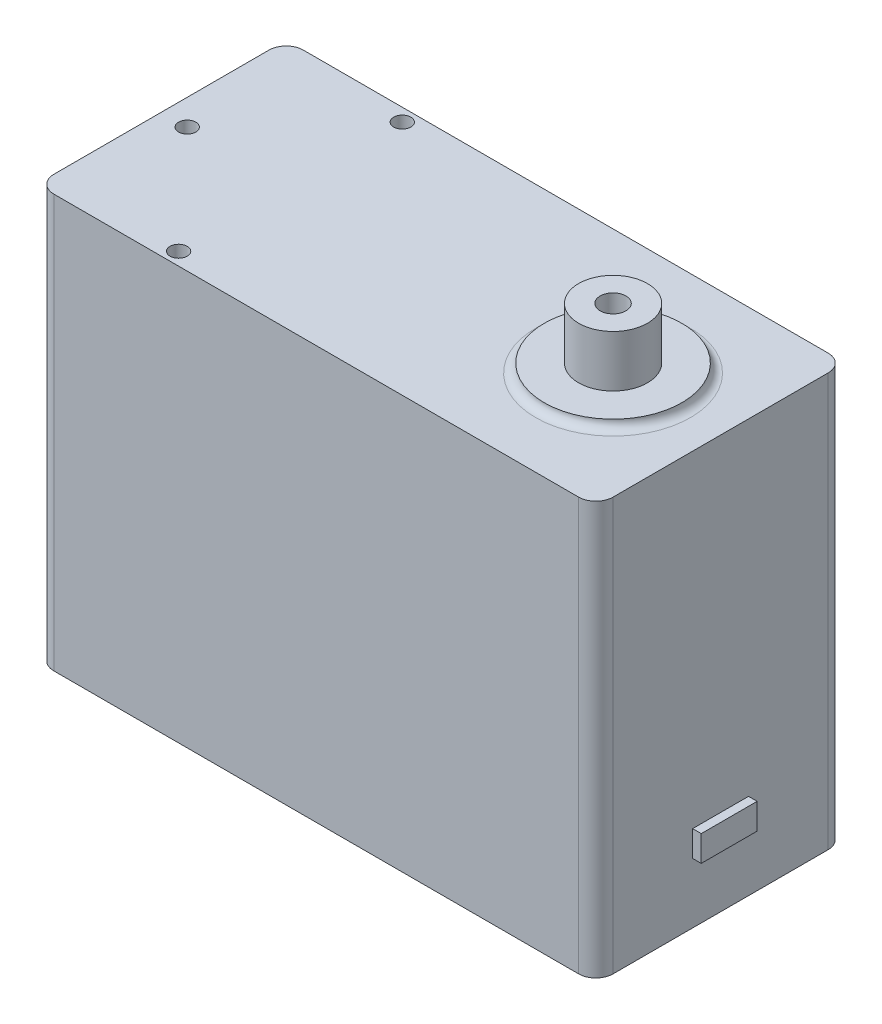
SolidWorks part; units mm, degrees
ref_plane "正面" through (0, 0, 0) normal (0, 0, 1) x (1, 0, 0)
ref_plane "平面" through (0, 0, 0) normal (0, 1, 0) x (1, 0, 0)
ref_plane "右側面" through (0, 0, 0) normal (1, 0, 0) x (0, 0, -1)
sketch "ｽｹｯﾁ2" plane through (0, 0, 0) normal (0, 1, 0) x (1, 0, 0)
  line L1 (-32.5, 14.5) -> (32.5, 14.5)
  line L2 (-32.5, 14.5) -> (-32.5, -14.5)
  line L3 (-32.5, -14.5) -> (32.5, -14.5)
  line L4 (32.5, 14.5) -> (32.5, -14.5)
  line L5 (-32.5, 14.5) -> (32.5, -14.5) construction
  line L6 (-32.5, -14.5) -> (32.5, 14.5) construction
  point P0 (0, 0)
  dimension "D1" = 65
  dimension "D2" = 29
extrude "ﾎﾞｽ - 押し出し1" add sketch "ｽｹｯﾁ2" along normal mid plane 48
fillet "ﾌｨﾚｯﾄ1" radius 2 4 edges at (32.5, 0, -14.5) (32.5, 0, 14.5) (-32.5, 0, 14.5) (-32.5, 0, -14.5)
sketch "ｽｹｯﾁ3" plane through (0, 24, 0) normal (0, 1, 0) x (1, 0, 0)
  line L0 (-32.5, 12.5) -> (-32.5, -12.5) construction
  line L1 (30.5, 14.5) -> (-30.5, 14.5) construction
  line L2 (-30.5, -14.5) -> (30.5, -14.5) construction
  line L3 (-26.4, 0) -> (26.4, 0) construction
  circle A0 centre (-29.5, 0) radius 1
  circle A1 centre (-17.5, -13) radius 1
  circle A2 centre (-17.5, 13) radius 1
  dimension "D1" = 2
  dimension "D4" = 2
  dimension "D2" = 3
  dimension "D3" = 14.5
  dimension "D5" = 15
  dimension "D6" = 1.5
extrude "ｶｯﾄ - 押し出し1" cut sketch "ｽｹｯﾁ3" against normal blind 6
sketch "ｽｹｯﾁ4" plane through (0, 24, 0) normal (0, 1, 0) x (1, 0, 0)
  line L0 (32.5, -12.5) -> (32.5, 12.5) construction
  line L1 (-30.5, -14.5) -> (30.5, -14.5) construction
  circle A0 centre (20, 0) radius 8
  dimension "D1" = 16
  dimension "D2" = 12.5
  dimension "D3" = 14.5
extrude "ﾎﾞｽ - 押し出し2" add sketch "ｽｹｯﾁ4" along normal blind 1
fillet "ﾌｨﾚｯﾄ2" radius 1 1 edges at (20, 24, 8)
sketch "ｽｹｯﾁ5" plane through (0, 25, 0) normal (0, 1, 0) x (1, 0, 0)
  circle A0 centre (20, 0) radius 4
  circle A1 centre (20, 0) radius 8 construction
  dimension "D1" = 0
  dimension "D2" = 8
extrude "ﾎﾞｽ - 押し出し3" add sketch "ｽｹｯﾁ5" along normal blind 6
sketch "ｽｹｯﾁ6" plane through (0, -24, 0) normal (0, -1, 0) x (1, 0, 0)
  line L0 (-32.5, -12.5) -> (-32.5, 12.5) construction
  line L1 (-30.5, 14.5) -> (30.5, 14.5) construction
  line L2 (30.25, 0) -> (-30.25, 0) construction
  line L3 (0, -15.95) -> (0, 15.95) construction
  circle A0 centre (-29.5, 13) radius 1
  circle A1 centre (-29.5, -13) radius 1
  circle A2 centre (29.5, -13) radius 1
  circle A3 centre (29.5, 13) radius 1
  circle A4 centre (-5.5, 13) radius 1
  circle A5 centre (-5.5, -13) radius 1
  dimension "D1" = 2
  dimension "D4" = 2
  dimension "D2" = 3
  dimension "D3" = 1.5
  dimension "D5" = 27
  dimension "D6" = 1.5
extrude "ｶｯﾄ - 押し出し2" cut sketch "ｽｹｯﾁ6" against normal blind 6
sketch "ｽｹｯﾁ7" plane through (0, -24, 0) normal (0, -1, 0) x (1, 0, 0)
  line L0 (32.5, 12.5) -> (32.5, -12.5) construction
  line L1 (30.5, -14.5) -> (-30.5, -14.5) construction
  circle A0 centre (20, 0) radius 8
  dimension "D1" = 16
  dimension "D2" = 12.5
  dimension "D3" = 14.5
extrude "ﾎﾞｽ - 押し出し4" add sketch "ｽｹｯﾁ7" along normal blind 1
fillet "ﾌｨﾚｯﾄ3" radius 1 1 edges at (20, -24, 8)
sketch "ｽｹｯﾁ8" plane through (0, -25, 0) normal (0, -1, 0) x (1, 0, 0)
  circle A0 centre (20, 0) radius 3.5
  dimension "D1" = 7
extrude "ﾎﾞｽ - 押し出し5" add sketch "ｽｹｯﾁ8" along normal blind 0.3
sketch "ｽｹｯﾁ9" plane through (0, -25, 0) normal (0, -1, 0) x (1, 0, 0)
  line L0 (30.5, -14.5) -> (-30.5, -14.5) construction
  line L1 (32.5, 12.5) -> (32.5, -12.5) construction
  circle A0 centre (20, 0) radius 3
  dimension "D1" = 6
  dimension "D2" = 14.5
  dimension "D3" = 12.5
extrude "ﾎﾞｽ - 押し出し6" add sketch "ｽｹｯﾁ9" along normal blind 5.5
sketch "ｽｹｯﾁ10" plane through (0, -30.5, 0) normal (0, -1, 0) x (1, 0, 0)
  circle A0 centre (20, 0) radius 1
  dimension "D1" = 2
extrude "ｶｯﾄ - 押し出し3" cut sketch "ｽｹｯﾁ10" against normal blind 5.5
sketch "ｽｹｯﾁ11" plane through (32.5, 0, 0) normal (1, 0, 0) x (0, 0, -1)
  line L0 (-12.5, -24) -> (12.5, -24) construction
  line L1 (-3.25, -14) -> (3.25, -14)
  line L2 (-3.25, -14) -> (-3.25, -17)
  line L3 (-3.25, -17) -> (3.25, -17)
  line L4 (3.25, -14) -> (3.25, -17)
  line L5 (-3.25, -14) -> (3.25, -17) construction
  line L6 (-3.25, -17) -> (3.25, -14) construction
  line L7 (14.5, 24) -> (14.5, -24) construction
  point P0 (0, -15.5)
  dimension "D1" = 10
  dimension "D2" = 3
  dimension "D3" = 6.5
  dimension "D4" = 14.5
extrude "ﾎﾞｽ - 押し出し7" add sketch "ｽｹｯﾁ11" along normal blind 1
sketch "ｽｹｯﾁ12" plane through (0, 31, 0) normal (0, 1, 0) x (1, 0, 0)
  circle A0 centre (20, 0) radius 1.5
  dimension "D1" = 3
extrude "ｶｯﾄ - 押し出し4" cut sketch "ｽｹｯﾁ12" against normal blind 6
